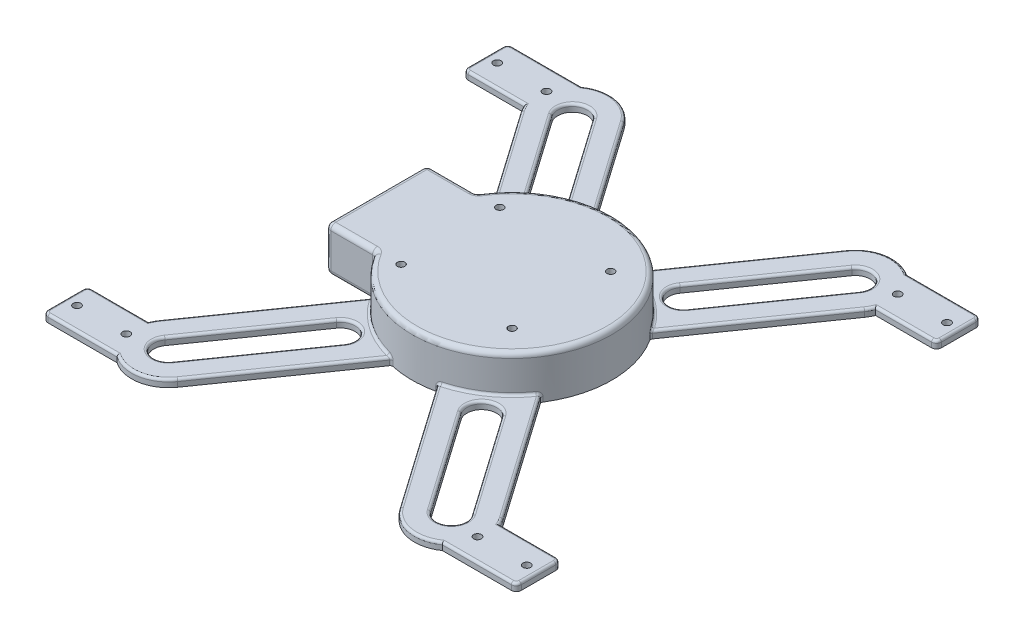
SolidWorks part; units mm, degrees
ref_plane "Front Plane" through (0, 0, 0) normal (0, 0, 1) x (1, 0, 0)
ref_plane "Top Plane" through (0, 0, 0) normal (0, 1, 0) x (1, 0, 0)
ref_plane "Right Plane" through (0, 0, 0) normal (1, 0, 0) x (0, 0, -1)
sketch "Sketch1" plane through (0, 0, 0) normal (0, 1, 0) x (1, 0, 0)
  circle A0 centre (0, 0) radius 37.5
  dimension "D1" = 75
extrude "Boss-Extrude1" add sketch "Sketch1" against normal blind 10
sketch "Sketch2" plane through (0, -10, 0) normal (0, -1, 0) x (1, 0, 0)
  line L1 (-58, -31.863) -> (-28.2443, -31.863)
  line L2 (-60, -29.863) -> (-60, 29.863)
  line L3 (-58, 31.863) -> (-28.2443, 31.863)
  line L5 (-60, -31.863) -> (-25, 31.863) construction
  line L6 (-60, 31.863) -> (-25, -31.863) construction
  arc A0 (-28.2443, -31.863) -> (-22.6514, -33.5733) centre (-28.2443, -41.863) cw
  arc A1 (-28.2443, 31.863) -> (-22.6514, 33.5733) centre (-28.2443, 41.863) ccw
  circle A2 centre (0, 0) radius 40.5
  arc A3 (-22.6514, -33.5733) -> (-22.6514, 33.5733) centre (0, 0) ccw
  arc A4 (-58, -31.863) -> (-60, -29.863) centre (-58, -29.863) cw
  arc A5 (-60, 29.863) -> (-58, 31.863) centre (-58, 29.863) cw
  point P0 (-42.5, 0)
  dimension "D4" = 10
  dimension "D5" = 2
  dimension "D2" = 60
  dimension "D3" = 35
  dimension "D1" = 3
extrude "Boss-Extrude2" add sketch "Sketch2" along normal blind 25
sketch "Sketch5" plane through (0, -35, 0) normal (0, -1, 0) x (1, 0, 0)
  circle A2 centre (0, 0) radius 32.5
  circle A3 centre (0, 0) radius 32.5
  dimension "D1" = 5
extrude "Boss-Extrude3" add sketch "Sketch5" along normal blind 2 contours A3
sketch "Sketch6" plane through (0, -37, 0) normal (0, -1, 0) x (1, 0, 0)
  circle A3 centre (0, 0) radius 40.5
  circle A4 centre (0, 0) radius 40.5
  dimension "D1" = 8
extrude "Boss-Extrude4" add sketch "Sketch6" along normal blind 15
sketch "Sketch7" plane through (0, -52, 0) normal (0, -1, 0) x (1, 0, 0)
  line L0 (0, 0) -> (57.3576, 81.9152) construction
  line L1 (-96.8158, 0) -> (96.8158, 0) construction
  line L2 (45.0704, 90.5189) -> (69.6449, 73.3116) construction
  line L3 (45.0704, 90.5189) -> (9.2906, 39.42)
  line L4 (69.6449, 73.3116) -> (33.8651, 22.2127)
  line L5 (28.6788, 40.9576) -> (57.3576, 81.9152) construction
  line L6 (23.7639, 44.3991) -> (52.4427, 85.3567)
  line L7 (33.5937, 37.5161) -> (62.2726, 78.4737)
  line L8 (0, 80.4612) -> (0, -73.163) construction
  line L9 (28.6788, -40.9576) -> (57.3576, -81.9152) construction
  line L10 (23.7639, -44.3991) -> (52.4427, -85.3567)
  line L11 (33.5937, -37.5161) -> (62.2726, -78.4737)
  line L12 (45.0704, -90.5189) -> (69.6449, -73.3116) construction
  line L13 (0, 0) -> (57.3576, -81.9152) construction
  line L14 (69.6449, -73.3116) -> (33.8651, -22.2127)
  line L15 (45.0704, -90.5189) -> (9.2906, -39.42)
  line L16 (-28.6788, 40.9576) -> (-57.3576, 81.9152) construction
  line L17 (-23.7639, 44.3991) -> (-52.4427, 85.3567)
  line L18 (-33.5937, 37.5161) -> (-62.2726, 78.4737)
  line L19 (-28.6788, -40.9576) -> (-57.3576, -81.9152) construction
  line L20 (-23.7639, -44.3991) -> (-52.4427, -85.3567)
  line L21 (-33.5937, -37.5161) -> (-62.2726, -78.4737)
  line L22 (-45.0704, -90.5189) -> (-9.2906, -39.42)
  line L23 (0, 0) -> (-57.3576, -81.9152) construction
  line L24 (-45.0704, -90.5189) -> (-69.6449, -73.3116) construction
  line L25 (-45.0704, 90.5189) -> (-69.6449, 73.3116) construction
  line L26 (0, 0) -> (-57.3576, 81.9152) construction
  line L27 (-69.6449, -73.3116) -> (-33.8651, -22.2127)
  line L28 (-69.6449, 73.3116) -> (-33.8651, 22.2127)
  line L29 (-45.0704, 90.5189) -> (-9.2906, 39.42)
  circle A0 centre (0, 0) radius 40.5 construction
  arc A1 (-33.8651, 22.2127) -> (-33.8651, -22.2127) centre (0, 0) ccw
  arc A2 (69.6449, 73.3116) -> (45.0704, 90.5189) centre (57.3576, 81.9152) ccw
  arc A3 (23.7639, 44.3991) -> (33.5937, 37.5161) centre (28.6788, 40.9576) ccw
  arc A4 (62.2726, 78.4737) -> (52.4427, 85.3567) centre (57.3576, 81.9152) ccw
  arc A5 (23.7639, -44.3991) -> (33.5937, -37.5161) centre (28.6788, -40.9576) cw
  arc A6 (62.2726, -78.4737) -> (52.4427, -85.3567) centre (57.3576, -81.9152) cw
  arc A7 (69.6449, -73.3116) -> (45.0704, -90.5189) centre (57.3576, -81.9152) cw
  arc A8 (-23.7639, 44.3991) -> (-33.5937, 37.5161) centre (-28.6788, 40.9576) cw
  arc A9 (-62.2726, 78.4737) -> (-52.4427, 85.3567) centre (-57.3576, 81.9152) cw
  arc A10 (-23.7639, -44.3991) -> (-33.5937, -37.5161) centre (-28.6788, -40.9576) ccw
  arc A11 (-62.2726, -78.4737) -> (-52.4427, -85.3567) centre (-57.3576, -81.9152) ccw
  arc A12 (-69.6449, -73.3116) -> (-45.0704, -90.5189) centre (-57.3576, -81.9152) ccw
  arc A13 (-69.6449, 73.3116) -> (-45.0704, 90.5189) centre (-57.3576, 81.9152) cw
  arc A14 (-9.2906, -39.42) -> (9.2906, -39.42) centre (0, 0) ccw
  arc A15 (33.8651, -22.2127) -> (33.8651, 22.2127) centre (0, 0) ccw
  arc A16 (9.2906, 39.42) -> (-9.2906, 39.42) centre (0, 0) ccw
  point P6 (0, 0)
  point P11 (57.3576, 81.9152)
  point P13 (43.0182, 61.4364)
  point P23 (43.0182, -61.4364)
  point P35 (-43.0182, 61.4364)
  point P42 (-43.0182, -61.4364)
  dimension "D2" = 30
  dimension "D4" = 6
  dimension "D1" = 55
  dimension "D3" = 100
extrude "Boss-Extrude5" add sketch "Sketch7" along normal blind 3 separate body
sketch "Sketch8" plane through (0, -55, 0) normal (0, -1, 0) x (1, 0, 0)
  circle A0 centre (0, 0) radius 5
  dimension "D1" = 10
extrude "Cut-Extrude1" cut sketch "Sketch8" against normal blind 6
sketch "Sketch9" plane through (0, -49, 0) normal (0, -1, 0) x (1, 0, 0)
  circle A0 centre (0, 0) radius 4
  dimension "D1" = 8
extrude "Boss-Extrude6" add sketch "Sketch9" along normal blind 8
sketch "Sketch10" plane through (0, -57, 0) normal (0, -1, 0) x (1, 0, 0)
  line L1 (3, 0) -> (1.5, 2.5981)
  line L2 (1.5, 2.5981) -> (-1.5, 2.5981)
  line L3 (-1.5, 2.5981) -> (-3, 0)
  line L4 (-3, 0) -> (-1.5, -2.5981)
  line L5 (-1.5, -2.5981) -> (1.5, -2.5981)
  line L6 (1.5, -2.5981) -> (3, 0)
  circle A0 centre (0, 0) radius 2.5981 construction
  dimension "D1" = 3
extrude "Cut-Extrude2" cut sketch "Sketch10" against normal blind 4
sketch "Sketch11" plane through (0, -55, 0) normal (0, -1, 0) x (1, 0, 0)
  line L0 (0, 0) -> (25.2374, 36.0427) construction
  arc A0 (23.7639, 44.3991) -> (33.5937, 37.5161) centre (28.6788, 40.9576) ccw construction
  circle A1 centre (17.8372, 25.4742) radius 2.5
  dimension "D1" = 5
extrude "Boss-Extrude7" add sketch "Sketch11" along normal blind 4
sketch "Sketch12" plane through (0, -59, 0) normal (0, -1, 0) x (1, 0, 0)
  line L1 (19.3372, 25.4742) -> (18.5872, 26.7732)
  line L2 (18.5872, 26.7732) -> (17.0872, 26.7732)
  line L3 (17.0872, 26.7732) -> (16.3372, 25.4742)
  line L4 (16.3372, 25.4742) -> (17.0872, 24.1752)
  line L5 (17.0872, 24.1752) -> (18.5872, 24.1752)
  line L6 (18.5872, 24.1752) -> (19.3372, 25.4742)
  circle A0 centre (17.8372, 25.4742) radius 1.299 construction
  dimension "D1" = 1.5
extrude "Cut-Extrude3" cut sketch "Sketch12" against normal blind 2
mirror "Mirror1" about plane through (0, 0, 0) normal (0, 0, 1) of "Cut-Extrude3", "Boss-Extrude7"
mirror "Mirror2" about plane through (0, 0, 0) normal (1, 0, 0) of "Mirror1", "Boss-Extrude7", "Cut-Extrude3"
sketch "Sketch13" plane through (0, 0, 0) normal (0, 1, 0) x (1, 0, 0)
  line L0 (0, -43.6546) -> (-77.9789, -43.6546)
  line L1 (-77.9789, -43.6546) -> (-77.9789, 38.8482)
  line L2 (-77.9789, 38.8482) -> (-19.9133, 38.8482)
  arc A0 (0, -43.6546) -> (-19.9133, 38.8482) centre (0, 0) ccw
extrude "Cut-Extrude5" cut sketch "Sketch13" against normal blind 37
sketch "Sketch14" plane through (0, -55, 0) normal (0, -1, 0) x (1, 0, 0)
  line L1 (65.9613, 94.2025) -> (95.9613, 94.2025)
  line L2 (65.9613, 94.2025) -> (65.9613, 76.2025)
  line L3 (65.9613, 76.2025) -> (95.9613, 76.2025)
  line L4 (95.9613, 94.2025) -> (95.9613, 76.2025)
  line L5 (-65.9613, 94.2025) -> (-95.9613, 94.2025)
  line L6 (-65.9613, 94.2025) -> (-65.9613, 76.2025)
  line L7 (-65.9613, 76.2025) -> (-95.9613, 76.2025)
  line L8 (-95.9613, 94.2025) -> (-95.9613, 76.2025)
  line L9 (65.9613, -94.2025) -> (95.9613, -94.2025)
  line L10 (65.9613, -94.2025) -> (65.9613, -76.2025)
  line L11 (65.9613, -76.2025) -> (95.9613, -76.2025)
  line L12 (95.9613, -94.2025) -> (95.9613, -76.2025)
  line L13 (-65.9613, -94.2025) -> (-95.9613, -94.2025)
  line L14 (-65.9613, -94.2025) -> (-65.9613, -76.2025)
  line L15 (-65.9613, -76.2025) -> (-95.9613, -76.2025)
  line L16 (-95.9613, -94.2025) -> (-95.9613, -76.2025)
  arc A0 (69.6449, 73.3116) -> (45.0704, 90.5189) centre (57.3576, 81.9152) ccw construction
  arc A1 (-45.0704, 90.5189) -> (-69.6449, 73.3116) centre (-57.3576, 81.9152) ccw construction
  arc A2 (45.0704, -90.5189) -> (69.6449, -73.3116) centre (57.3576, -81.9152) ccw construction
  arc A3 (-69.6449, -73.3116) -> (-45.0704, -90.5189) centre (-57.3576, -81.9152) ccw construction
  dimension "D1" = 30
  dimension "D2" = 18
  dimension "D3" = 30
  dimension "D4" = 18
  dimension "D5" = 30
  dimension "D6" = 18
  dimension "D7" = 18
  dimension "D8" = 30
extrude "Boss-Extrude8" add sketch "Sketch14" against normal up to surface (3 mm away) up to face at (-43.0182, -52, 61.4364)
fillet "Fillet1" radius 1 56 edges at (33.8651, -53.5, -22.2127) (9.2906, -53.5, -39.42) (9.2906, -53.5, 39.42) (33.8651, -53.5, 22.2127) (-33.8651, -53.5, 22.2127) (-9.2906, -53.5, 39.42) (-9.2906, -53.5, -39.42) (-33.8651, -53.5, -22.2127) (47.9331, -52, -57.9949) (60.7991, -52, -86.8301) (38.1033, -52, -64.8779) (25.2374, -52, -36.0427) (95.9613, -52, -85.2025) (83.5942, -52, -76.2025) (70.5157, -52, -74.7134) (51.755, -52, -47.7621) (23.2298, -52, -33.1757) (27.1805, -52, -64.9694) (54.7529, -52, -96.6873) (80.9613, -52, -94.2025) (27.1805, -52, 64.9694) (23.2298, -52, 33.1757) (51.755, -52, 47.7621) (70.5157, -52, 74.7134) (83.5942, -52, 76.2025) (95.9613, -52, 85.2025) (80.9613, -52, 94.2025) (54.7529, -52, 96.6873) (38.1033, -52, 64.8779) (60.7991, -52, 86.8301) (47.9331, -52, 57.9949) (25.2374, -52, 36.0427) (-47.9331, -52, 57.9949) (-60.7991, -52, 86.8301) (-38.1033, -52, 64.8779) (-25.2374, -52, 36.0427) (-95.9613, -52, 85.2025) (-83.5942, -52, 76.2025) (-70.5157, -52, 74.7134) (-51.755, -52, 47.7621) (-23.2298, -52, 33.1757) (-27.1805, -52, 64.9694) (-54.7529, -52, 96.6873) (-80.9613, -52, 94.2025) (-27.1805, -52, -64.9694) (-23.2298, -52, -33.1757) (-51.755, -52, -47.7621) (-70.5157, -52, -74.7134) (-83.5942, -52, -76.2025) (-95.9613, -52, -85.2025) (-80.9613, -52, -94.2025) (-54.7529, -52, -96.6873) (-38.1033, -52, -64.8779) (-60.7991, -52, -86.8301) (-47.9331, -52, -57.9949) (-25.2374, -52, -36.0427)
fillet "Fillet3" radius 2 16 edges at (95.6684, -52.2929, -93.9096) (95.6684, -52.2929, -76.4954) (95.6684, -52.2929, 93.9096) (95.6684, -52.2929, 76.4954) (-95.6684, -52.2929, 93.9096) (-95.6684, -52.2929, 76.4954) (-95.6684, -52.2929, -76.4954) (-95.6684, -52.2929, -93.9096) (-95.9613, -54, -94.2025) (-95.9613, -54, -76.2025) (-95.9613, -54, 76.2025) (-95.9613, -54, 94.2025) (95.9613, -54, 76.2025) (95.9613, -54, 94.2025) (95.9613, -54, -76.2025) (95.9613, -54, -94.2025)
ref_plane "Plane1" through (-55, 0, 0) normal (1, 0, 0) x (0, 0, -1)
sketch "Sketch15" plane through (-55, 0, 0) normal (1, 0, 0) x (0, 0, -1)
  line L0 (40.5, -37) -> (-40.5, -37) construction
  line L1 (-20.5, -37) -> (20.5, -37)
  line L2 (-20.5, -37) -> (-20.5, -55)
  line L3 (-20.5, -55) -> (20.5, -55)
  line L4 (20.5, -37) -> (20.5, -55)
  line L5 (-21.6548, -55) -> (21.6548, -55) construction
  line L6 (-40.5, -37) -> (-40.5, -55) construction
  line L7 (40.5, -55) -> (40.5, -37) construction
  dimension "D1" = 20
  dimension "D2" = 20
extrude "Boss-Extrude9" add sketch "Sketch15" along normal up to surface (20.0715 mm away) up to face at (0, -52.9049, 0)
fillet "Fillet4" radius 2 19 edges at (-70.5157, -55, 74.7134) (-70.5157, -55, -74.7134) (-51.9477, -55, 48.0373) (-51.9477, -55, -48.0373) (-34.0699, -55, 22.2128) (-34.0699, -55, -22.2128) (-34.5814, -55, 21.0803) (-34.5814, -55, -21.0803) (-44.9642, -37, 20.5) (-44.9642, -37, -20.5) (-55, -46, 20.5) (-55, -46, -20.5) (-55, -55, 0) (-44.9642, -55, 20.5) (-44.9642, -55, -20.5) (-55, -37, 0) (-34.9285, -46, 20.5) (-34.9285, -46, -20.5) (40.5, -37, 0)
sketch "Sketch16" plane through (0, -37, 0) normal (0, 1, 0) x (1, 0, 0)
  circle A0 centre (-24.9571, 20) radius 1.5
  circle A1 centre (20.0429, 20) radius 1.5
  circle A2 centre (20.0429, -20) radius 1.5
  circle A3 centre (-24.9571, -20) radius 1.5
  dimension "D1" = 3
extrude "Cut-Extrude6" cut sketch "Sketch16" against normal blind 10
sketch "Sketch17" plane through (0, -55, 0) normal (0, -1, 0) x (1, 0, 0)
  circle A0 centre (91.2113, 85.2025) radius 1.55
  circle A1 centre (71.2113, 85.2025) radius 1.55
  circle A2 centre (-71.2113, 85.2025) radius 1.55
  circle A3 centre (-91.2113, 85.2025) radius 1.55
  circle A4 centre (91.2113, -85.2025) radius 1.55
  circle A5 centre (71.2113, -85.2025) radius 1.55
  circle A6 centre (-71.2113, -85.2025) radius 1.55
  circle A7 centre (-91.2113, -85.2025) radius 1.55
  dimension "D1" = 3.1
extrude "Cut-Extrude7" cut sketch "Sketch17" against normal blind 10
sketch "Sketch18" plane through (-55, 0, 0) normal (-1, 0, 0) x (0, 0, 1)
  circle A0 centre (-14, -46) radius 1.5
  circle A1 centre (14, -46) radius 1.5
  dimension "D1" = 3
extrude "Cut-Extrude8" cut sketch "Sketch18" against normal blind 10
sketch "Sketch19" plane through (0, -59, 0) normal (0, -1, 0) x (1, 0, 0)
  line L1 (-22.9763, 30.5906) -> (22.7092, 30.5906)
  line L2 (-22.9763, 30.5906) -> (-22.9763, -32.7279)
  line L3 (-22.9763, -32.7279) -> (22.7092, -32.7279)
  line L4 (22.7092, 30.5906) -> (22.7092, -32.7279)
extrude "Cut-Extrude9" cut sketch "Sketch19" against normal up to surface (4 mm away) up to face at (91.2113, -55, -86.7525)
